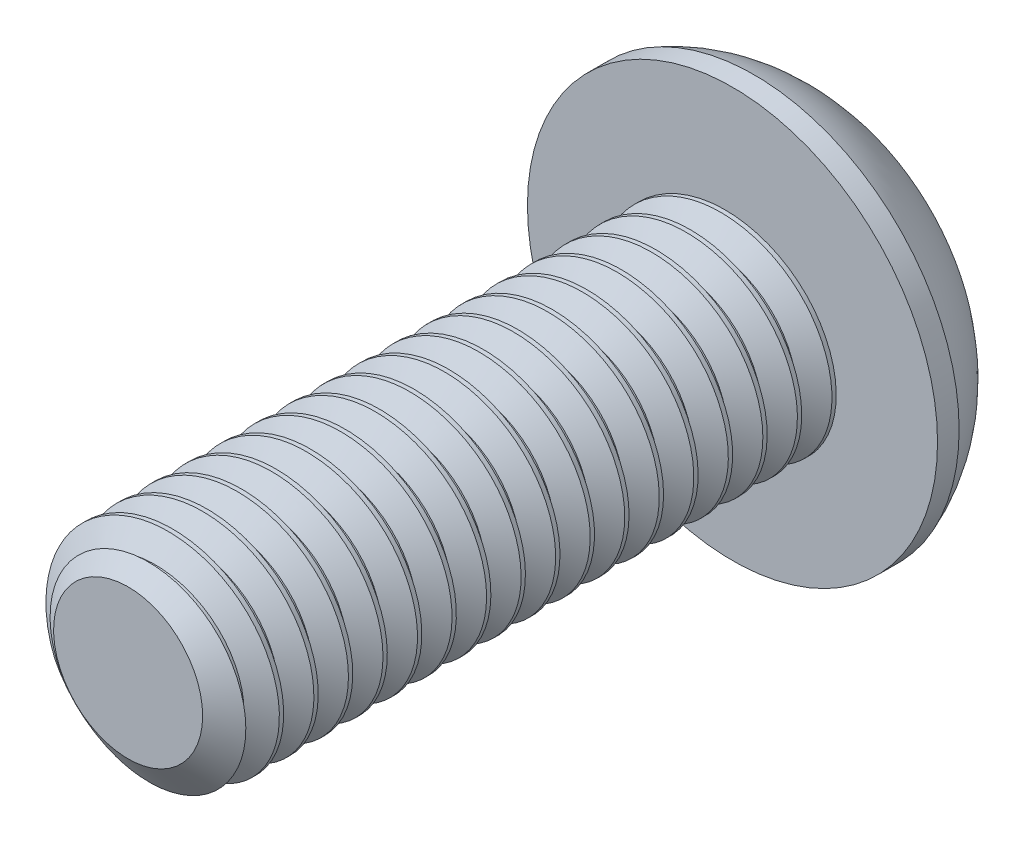
SolidWorks part; units mm, degrees
ref_plane "Front Plane" through (0, 0, 0) normal (0, 0, 1) x (1, 0, 0)
ref_plane "Top Plane" through (0, 0, 0) normal (0, 1, 0) x (1, 0, 0)
ref_plane "Right Plane" through (0, 0, 0) normal (1, 0, 0) x (0, 0, -1)
sketch "Sketch1" plane through (0, 0, 0) normal (0, 0, 1) x (1, 0, 0)
  circle A0 centre (0, 0) radius 2.5
  dimension "OD" = 5
extrude "Extrude1" add sketch "Sketch1" against normal blind 14
sketch "Sketch2" plane through (0, 0, 0) normal (0, 0, 1) x (1, 0, 0)
  circle A0 centre (0, 0) radius 2.5 construction
  circle A1 centre (0, 0) radius 2.5
curve "Helix/Spiral1" pitch 0.8 height 14.8 turns 18.5 parameters "pitch"=0.8
sketch "Sketch3" plane through (0, 0, 0) normal (1, 0, 0) x (0, 0, -1)
  line L0 (-0.7, 2.5) -> (-0.4, 1.9804)
  line L1 (-0.4, 1.9804) -> (-0.3, 1.9804)
  line L2 (-0.3, 1.9804) -> (0, 2.5)
  line L3 (-0.7, 2.5) -> (0, 2.5)
  line L4 (-0.35, 2.5) -> (-0.35, 1.9804) construction
  line L5 (-0.55, 2.2402) -> (-0.15, 2.2402) construction
  line L6 (0, 2.5) -> (0, -2.5) construction
  dimension "D1" = 0.1
  dimension "D2" = 0.4
  dimension "D3" = 60
sweep "Cut-Sweep1" cut profiles "Sketch3" path "Helix/Spiral1"
sketch "Sketch4" plane through (0, 0, 0) normal (1, 0, 0) x (0, 0, -1)
  line L0 (0.5417, 2.5) -> (0, 1.7264)
  line L1 (0, 1.7264) -> (0, 2.5)
  line L2 (0.5417, 2.5) -> (0, 2.5)
  line L3 (-0.7, 2.5) -> (0, 2.5) construction
  line L4 (0, 0) -> (7.0209, 0) construction
  dimension "D1" = 55
  dimension "D2" = 0.254
revolve "Cut-Revolve1" cut sketch "Sketch4" angle 360 about L4
sketch "Sketch5" plane through (0, 0, 0) normal (1, 0, 0) x (0, 0, -1)
  line L0 (14, -1.7838) -> (14, 1.991) construction
  line L1 (14, 2.627) -> (28.1202, 2.627)
  line L2 (14, 2.627) -> (14, 0)
  line L3 (14, 0) -> (28, 0)
  line L4 (28, 2.2968) -> (28, 0)
  line L5 (28.1202, 2.627) -> (28, 2.2968)
  line L6 (0, 0) -> (9.9695, 0) construction
  point P3 (28, 2.627)
  point P10 (28, 2.627)
  dimension "D1" = 0.3302
  dimension "Thread min" = 28
  dimension "D2" = 0.127
  dimension "D3" = 20
revolve "partially thread" [suppressed] add sketch "Sketch5" angle 360 about L6
sketch "Sketch6" plane through (0, 0, -14) normal (0, 0, -1) x (-1, 0, 0)
  circle A0 centre (0, 0) radius 4.75
  dimension "head dia" = 9.5
extrude "Extrude2" add sketch "Sketch6" along normal blind 2.75
sketch "Sketch10" plane through (0, 0, 0) normal (1, 0, 0) x (0, 0, -1)
  line L0 (16.75, -4.75) -> (16.75, 4.75) construction
  line L1 (0, 0) -> (15.9584, 0) construction
  line L2 (16.75, 4.75) -> (14, 4.75) construction
  line L3 (14, 4.75) -> (14, -4.75) construction
  line L4 (14.5, 4.75) -> (14.5, 5.25)
  line L5 (14.5, 5.25) -> (17.25, 5.25)
  line L6 (17.25, 5.25) -> (17.25, 1.5)
  line L7 (16.75, 1.5) -> (17.25, 1.5)
  arc A0 (16.75, 1.5) -> (14.5, 4.75) centre (13.2778, 1.5) ccw
  dimension "D1" = 3
  dimension "D2" = 0.5
  dimension "D3" = 0.5
revolve "Cut-Revolve2" cut sketch "Sketch10" angle 360 about L1
ref_plane "Plane1" through (0, 0, -16.75) normal (0, 0, 1) x (1, 0, 0)
sketch "Sketch7" plane through (0, 0, -16.75) normal (0, 0, -1) x (-1, 0, 0)
  line L1 (0, 1.7321) -> (-1.5, 0.866)
  line L2 (-1.5, 0.866) -> (-1.5, -0.866)
  line L3 (-1.5, -0.866) -> (0, -1.7321)
  line L4 (0, -1.7321) -> (1.5, -0.866)
  line L5 (1.5, -0.866) -> (1.5, 0.866)
  line L6 (1.5, 0.866) -> (0, 1.7321)
  circle A0 centre (0, 0) radius 1.5 construction
  dimension "hex dia" = 3
extrude "Cut-Extrude1" cut sketch "Sketch7" against normal blind 2.25
sketch "Sketch8" plane through (0, 0, -16.75) normal (0, 0, 1) x (1, 0, 0)
  circle A0 centre (0, 0) radius 1.7321
extrude "Cut-Extrude2" cut sketch "Sketch8" along normal through all draft 45
sketch "Sketch9" plane through (0, 0, 0) normal (1, 0, 0) x (0, 0, -1)
  line L0 (0, 2.5) -> (0, -2.5) construction
  line L1 (4.4, 2.5) -> (4.4, -2.5) construction
  dimension "D1" = 4.4
  dimension "D4" = 0.635
  dimension "D5" = 0.3302
equation "\"D3@Helix/Spiral1\" = \"screw length@Extrude1\"+\"pitch@Helix/Spiral1\""
equation "\"D1@Sketch3\" = \"pitch@Helix/Spiral1\"*.125"
equation "\"D2@Sketch3\" = \"pitch@Helix/Spiral1\"*.5"
equation "\"D1@Cut-Extrude1\" = \"hex dia@Sketch7\"*.75"
equation "\"D1@Sketch9\" = \"pitch@Helix/Spiral1\"*5.5"
equation "\"D1@Sketch10\" = \"hex dia@Sketch7\""
equation "\"D1@Plane1\" = \"head depth@Extrude2\""
